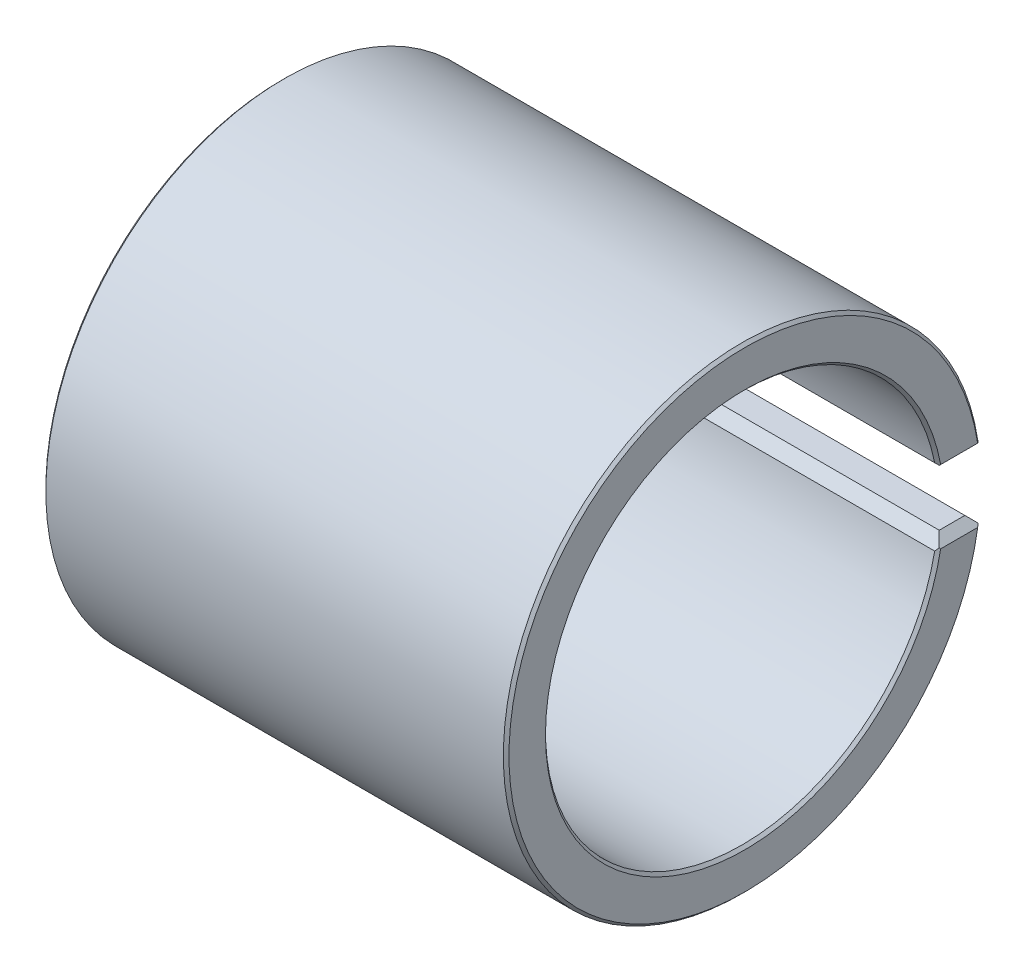
SolidWorks part; units mm, degrees
material "6061-T6 Aluminum"
ref_plane "Front Plane" through (0, 0, 0) normal (0, 0, 1) x (1, 0, 0)
ref_plane "Top Plane" through (0, 0, 0) normal (0, 1, 0) x (1, 0, 0)
ref_plane "Right Plane" through (0, 0, 0) normal (1, 0, 0) x (0, 0, -1)
sketch "Sketch1" plane through (0, 0, 0) normal (0, 0, 1) x (1, 0, 0)
  line L0 (-8.25, 7) -> (8.25, 7)
  line L1 (0, 7) -> (0, 0) construction
  line L2 (-8.25, 7) -> (-8.25, 8.5)
  line L3 (-8.25, 8.5) -> (8.25, 8.5)
  line L4 (8.25, 8.5) -> (8.25, 7)
  line L5 (0, 0) -> (5.8567, 0) construction
  dimension "D1" = 14
  dimension "D2" = 17
  dimension "D3" = 16.5
revolve "Revolve1" add sketch "Sketch1" angle 360 about L5
chamfer "Chamfer1" distance 0.1 angle 45 4 edges at (-8.25, 0, 8.5) (-8.25, 0, 7) (8.25, 0, 7) (8.25, 0, 8.5)
sketch "Sketch2" plane through (0, 0, 0) normal (0, 0, 1) x (1, 0, 0)
  line L1 (-21.9532, -1) -> (21.9532, -1)
  line L2 (-21.9532, -1) -> (-21.9532, 1)
  line L3 (-21.9532, 1) -> (21.9532, 1)
  line L4 (21.9532, -1) -> (21.9532, 1)
  line L5 (-21.9532, -1) -> (21.9532, 1) construction
  line L6 (-21.9532, 1) -> (21.9532, -1) construction
  point P0 (0, 0)
  dimension "D1" = 2
extrude "Cut-Extrude1" cut sketch "Sketch2" against normal through all
chamfer "Chamfer2" distance 0.3 angle 45 8 edges at (8.25, 1, -7.6847) (8.25, -1, -7.6847) (0, -1, -8.441) (0, 1, -8.441) (-8.25, 1, -7.6847) (-8.25, -1, -7.6847) (0, -1, -6.9282) (0, 1, -6.9282) first distance on face at (0, 1, -7.6847) first distance on face at (0, -1, -7.6847)
